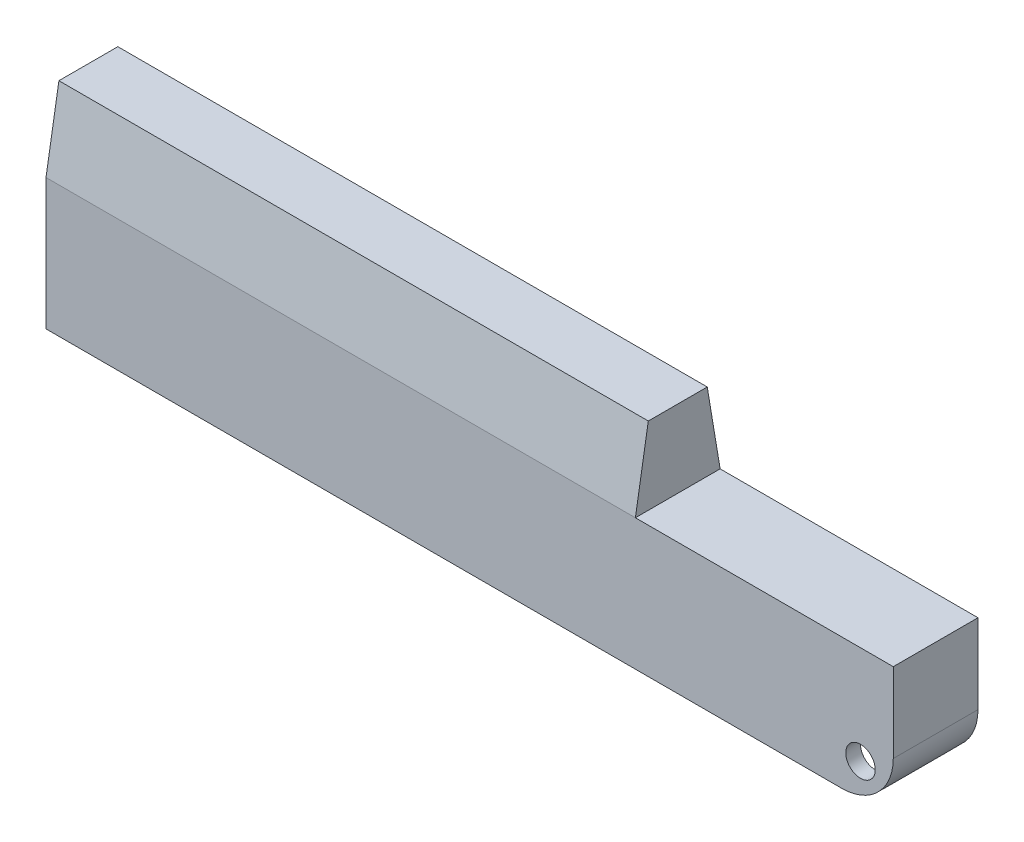
SolidWorks part; units mm, degrees
ref_plane "Front Plane" through (0, 0, 0) normal (0, 0, 1) x (1, 0, 0)
ref_plane "Top Plane" through (0, 0, 0) normal (0, 1, 0) x (1, 0, 0)
ref_plane "Right Plane" through (0, 0, 0) normal (1, 0, 0) x (0, 0, -1)
sketch "Sketch1" plane through (0, 0, 0) normal (0, 1, 0) x (1, 0, 0)
  line L1 (-69, -5.75) -> (69, -5.75)
  line L2 (-69, -5.75) -> (-69, 5.75)
  line L3 (-69, 5.75) -> (69, 5.75)
  line L4 (69, -5.75) -> (69, 5.75)
  line L5 (-69, -5.75) -> (69, 5.75) construction
  line L6 (-69, 5.75) -> (69, -5.75) construction
  point P0 (0, 0)
  dimension "D1" = 11.5
  dimension "D2" = 138
extrude "Boss-Extrude1" add sketch "Sketch1" against normal blind 17.8 contours L2 L3 L4 L1
sketch "Sketch8" plane through (0, 0, 5.75) normal (0, 0, 1) x (1, 0, 0)
  line L0 (69, 0) -> (51.2, -17.8) construction
  line L1 (-69, -17.8) -> (69, -17.8) construction
  line L3 (60.1, -8.9) -> (69, -8.9) construction
  line L4 (69, -17.8) -> (69, 0) construction
  line L5 (64.55, -8.9) -> (64.55, -17.8) construction
  circle A0 centre (64.55, -13.35) radius 2
  dimension "D1" = 4
extrude "Cut-Extrude4" cut sketch "Sketch8" against normal up to surface (11.5 mm away) up to face at (0, -8.9, -5.75)
sketch "Sketch11" plane through (0, -17.8, 0) normal (0, -1, 0) x (1, 0, 0)
  line L0 (-69, 5.75) -> (-69, -5.75)
  line L1 (-69, 5.75) -> (-46, 5.75)
  line L2 (-69, -5.75) -> (-46, -5.75)
  line L3 (-46, 5.75) -> (-46, -5.75)
  line L4 (69, 5.75) -> (69, -5.75) construction
  dimension "D1" = 115
extrude "Cut-Extrude5" cut sketch "Sketch11" against normal up to surface (17.8 mm away) up to face at (0, 0, 0)
sketch "Sketch14" plane through (0, 0, 0) normal (0, 1, 0) x (1, 0, 0)
  line L0 (-46, -5.75) -> (69, -5.75) construction
  line L1 (-46, 5.75) -> (34, 5.75)
  line L2 (-46, 5.75) -> (-46, -5.75)
  line L3 (-46, -5.75) -> (34, -5.75)
  line L4 (34, 5.75) -> (34, -5.75)
  dimension "D1" = 80
extrude "Boss-Extrude4" add sketch "Sketch14" along normal blind 10.5
chamfer "Chamfer1" distance 10.5 distance2 1.75 1 edges at (-6, 10.5, 5.75)
chamfer "Chamfer2" distance 10.5 distance2 1.75 1 edges at (-6, 10.5, -5.75)
sketch "Sketch12" plane through (0, -17.8, 0) normal (0, -1, 0) x (1, 0, 0)
  line L0 (-46, -5.75) -> (69, 5.75) construction
  line L1 (-46, 5.75) -> (69, -5.75) construction
  line L2 (69, 5.75) -> (69, -5.75) construction
  line L3 (-44, -3.75) -> (67, -3.75)
  line L4 (-44, -3.75) -> (-44, 3.75)
  line L5 (-44, 3.75) -> (67, 3.75)
  line L6 (67, -3.75) -> (67, 3.75)
  line L7 (-44, -3.75) -> (67, 3.75) construction
  line L8 (-44, 3.75) -> (67, -3.75) construction
  line L9 (-46, 5.75) -> (69, 5.75) construction
  point P8 (11.5, 0)
  dimension "D1" = 2
  dimension "D2" = 2
extrude "Cut-Extrude6" cut sketch "Sketch12" against normal offset from surface (9.8 mm away) 8 up to face at (51.5, 0, 0)
sketch "Sketch13" plane through (0, 0, -3.75) normal (0, 0, 1) x (1, 0, 0)
  line L1 (11.5, -17.8) -> (11.5, 1.1234) construction
  line L2 (-44, -17.8) -> (67, -17.8) construction
  line L3 (-44, -14.3) -> (-44, -12.3)
  line L4 (-44, -14.3) -> (11.5, -14.3)
  line L5 (-44, -12.3) -> (11.5, -12.3)
  line L6 (11.5, -14.3) -> (11.5, -12.3)
  line L7 (-44, -8) -> (-44, -17.8) construction
  dimension "D1" = 3.5
  dimension "D2" = 2
extrude "Boss-Extrude3" add sketch "Sketch13" along normal up to surface (7.5 mm away) up to face at (11.5, -12.9, 3.75)
fillet "Fillet1" radius 7 1 edges at (69, -17.8, 0)
